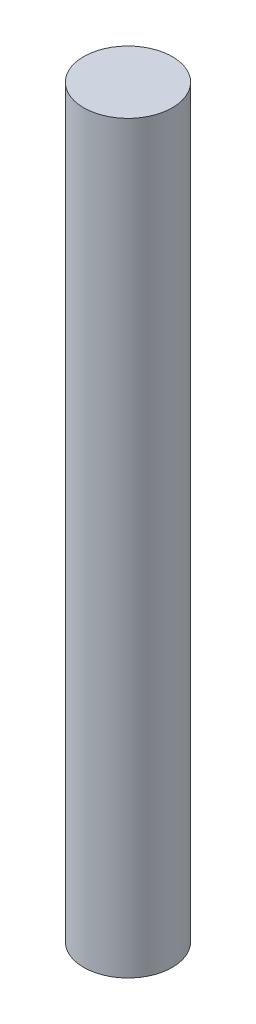
SolidWorks part; units mm, degrees
material "Alloy Steel"
ref_plane "Front Plane" through (0, 0, 0) normal (0, 0, 1) x (1, 0, 0)
ref_plane "Top Plane" through (0, 0, 0) normal (0, 1, 0) x (1, 0, 0)
ref_plane "Right Plane" through (0, 0, 0) normal (1, 0, 0) x (0, 0, -1)
sketch "Sketch1" plane through (0, 0, 0) normal (0, 1, 0) x (1, 0, 0)
  circle A0 centre (0, 0) radius 2.3813
  dimension "D1" = 4.7625
extrude "Boss-Extrude1" add sketch "Sketch1" along normal blind 40
